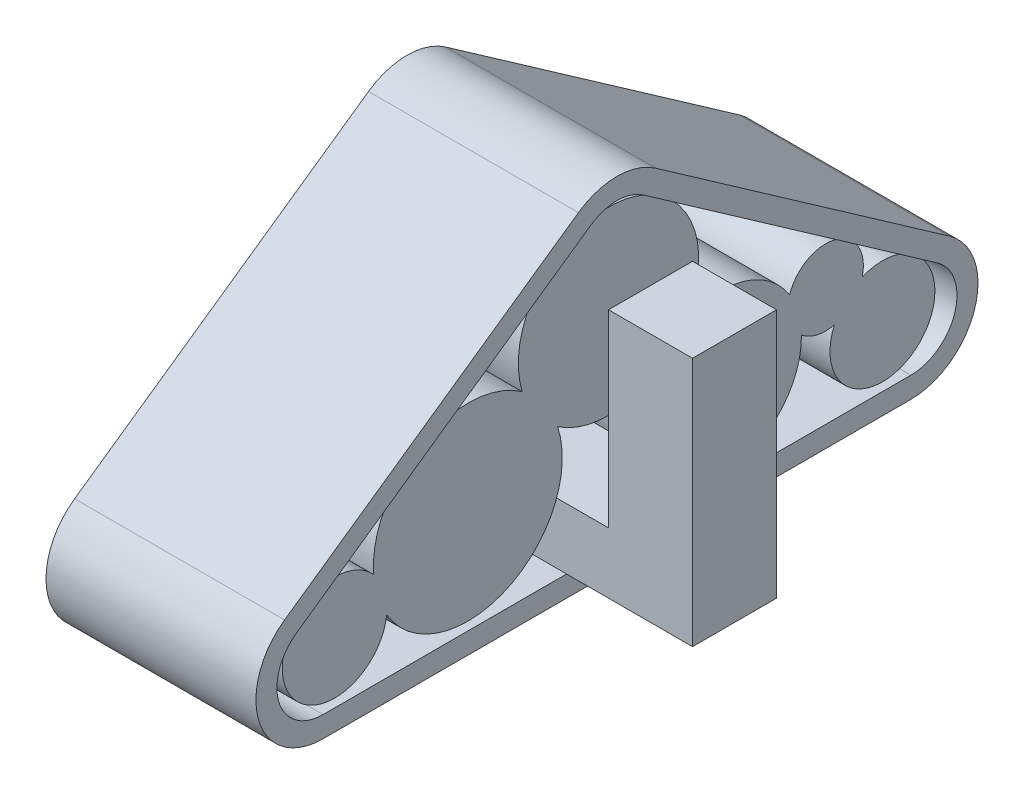
SolidWorks part; units mm, degrees
material "Polyethylene Cross-Linked"
ref_plane "Front" through (0, 0, 0) normal (0, 0, 1) x (1, 0, 0)
ref_plane "Top" through (0, 0, 0) normal (0, 1, 0) x (1, 0, 0)
ref_plane "Right" through (0, 0, 0) normal (1, 0, 0) x (0, 0, -1)
sketch "Sketch1" plane through (0, 0, 0) normal (1, 0, 0) x (0, 0, -1)
  line L0 (3, 0) -> (-3, 0)
  line L1 (6.641, 0) -> (-6.641, 0) construction
  line L2 (-3, 0) -> (-3.5, 0)
  line L3 (-3.9589, 1.4553) -> (-0.4589, 3.906)
  line L4 (0, 2.325) -> (0, -2.325) construction
  line L5 (3.9589, 1.4553) -> (0.4589, 3.906)
  line L6 (3, 0) -> (3.5, 0)
  line L8 (0.3155, 3.7013) -> (3.8155, 1.2505)
  line L9 (3.5, 0.25) -> (-3.5, 0.25)
  line L10 (-0.3155, 3.7013) -> (-3.8155, 1.2505)
  line L11 (0, 3.8797) -> (0, 3.2507)
  arc A0 (3.9589, 1.4553) -> (3.5, 0) centre (3.5, 0.8) cw
  arc A1 (-3.5, 0) -> (-3.9589, 1.4553) centre (-3.5, 0.8) cw
  arc A2 (-0.4589, 3.906) -> (0.4589, 3.906) centre (0, 3.2507) cw
  arc A3 (-3.8155, 1.2505) -> (-3.5, 0.25) centre (-3.5, 0.8) ccw
  arc A5 (3.8155, 1.2505) -> (3.5, 0.25) centre (3.5, 0.8) cw
  arc A6 (0.3155, 3.7013) -> (-0.3155, 3.7013) centre (0, 3.2507) ccw
  point P11 (0, 0)
  point P13 (6.0373, 0)
  point P16 (-6.0373, 0)
  point P19 (0, 4.2273)
  dimension "D2" = 0.8
  dimension "D4" = 0.8
  dimension "D5" = 1.1
  dimension "D6" = 1.1
  dimension "D1" = 7
  dimension "D3" = 35
  dimension "D7" = 0.25
extrude "Treads" add sketch "Sketch1" along normal blind 2.5 contours L8 A6 L10 A3 L9 A5 | L10 A3 L9 A5 L8 A6 | L3 A2 L5 A0 L6 L0 L2 A1 region at (0, 1.5312, 0)
ref_plane "Plane1" through (1.25, 0, 0) normal (1, 0, 0) x (0, 0, -1)
sketch "Sketch3" plane through (1.25, 0, 0) normal (1, 0, 0) x (0, 0, -1)
  line L0 (-0.3155, 3.7013) -> (-3.8155, 1.2505) construction
  line L1 (3.5, 0.25) -> (-3.5, 0.25) construction
  line L2 (0, 1.375) -> (0, -1.375) construction
  line L7 (-0.6, 0.25) -> (0.4, 0.25)
  line L8 (-0.6, 0.25) -> (-0.6, 0.975)
  line L9 (0.4, 0.25) -> (0.4, 0.975)
  line L10 (0.4, 0.975) -> (-0.6, 0.975)
  line L11 (0.3155, 3.7013) -> (3.8155, 1.2505) construction
  circle A0 centre (-3.2621, 0.875) radius 0.625
  circle A1 centre (3.2621, 0.875) radius 0.625
  circle A2 centre (-1.6763, 1.375) radius 1.125
  circle A3 centre (0, 2.6098) radius 1.075
  circle A4 centre (1.3472, 1.2) radius 0.95
  circle A5 centre (2.5852, 1.5627) radius 0.45
  point P6 (0, 0.5)
  dimension "D1" = 1.25
  dimension "D2" = 0.625
  dimension "D3" = 0.625
  dimension "D6" = 2.25
  dimension "D7" = 1.125
  dimension "D8" = 1.125
  dimension "D9" = 2.15
  dimension "D10" = 1.075
  dimension "D11" = 1.9
  dimension "D12" = 0.95
  dimension "D13" = 1.95
  dimension "D15" = 0.9
  dimension "D16" = 0.45
  dimension "D4" = 1
  dimension "D5" = 0.725
  dimension "D14" = 0.6
  dimension "D17" = 1.29
extrude "Circles" add sketch "Sketch3" along normal blind 1.15 and the other way blind 1.15 separate body contours A2 A0 | A3 A2 A0 | A4 A3 A2 | A5 A4 A3 | A4 A5 A1 | A4 A5 | A5 A1 | A1 A5 | A0 | A2 | A3 region at (1.25, 1.3684, 1.6806) region at (1.25, 0.8706, 3.2762) region at (1.25, 2.6251, -0.0074) region at (1.25, 1.1901, -1.3418) region at (1.25, 1.5871, -2.593) region at (1.25, 1.4527, -2.2099) region at (1.25, 0.8632, -3.2738) region at (1.25, 1.2825, -2.861)
extrude "Bottom of Connector" add sketch "Sketch3<5>" along normal blind 2.75 and the other way blind 1.25 contours L9 L10 L8 L7 region at (1.25, 0.6125, 0.1)
sketch "Sketch3<5>" plane through (1.25, 0, 0) normal (1, 0, 0) x (0, 0, -1) same geometry as "Sketch3"
sketch "Sketch4" plane through (0, 0.975, 0) normal (0, 1, 0) x (1, 0, 0)
  line L0 (0, -0.6) -> (4, -0.6) construction
  line L1 (4, 0.4) -> (3, 0.4)
  line L2 (4, 0.4) -> (4, -0.6)
  line L3 (4, -0.6) -> (3, -0.6)
  line L4 (3, 0.4) -> (3, -0.6)
  dimension "D1" = 1
extrude "Top of Connector" add sketch "Sketch4" along normal blind 2.25
